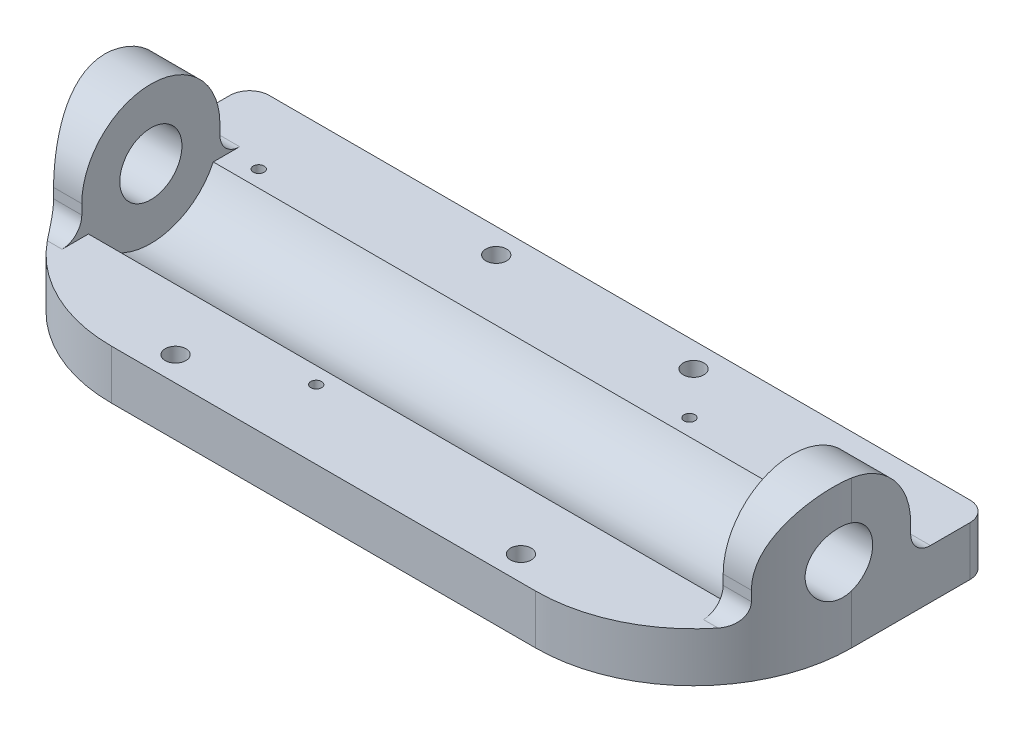
SolidWorks part; units mm, degrees
ref_plane "Front Plane" through (0, 0, 0) normal (0, 0, 1) x (1, 0, 0)
ref_plane "Top Plane" through (0, 0, 0) normal (0, 1, 0) x (1, 0, 0)
ref_plane "Right Plane" through (0, 0, 0) normal (1, 0, 0) x (0, 0, -1)
sketch "Sketch1" plane through (0, 0, 0) normal (1, 0, 0) x (0, 0, -1)
  line L0 (-12.6491, -6) -> (-30, -6)
  line L1 (-30, -6) -> (-30, -16)
  line L2 (-30, -16) -> (30, -16)
  line L3 (30, -16) -> (30, -6)
  line L4 (30, -6) -> (12.6491, -6)
  line L5 (0, 0) -> (0, -16) construction
  arc A0 (-12.6491, -6) -> (12.6491, -6) centre (0, 0) ccw
  dimension "D1" = 14
  dimension "D2" = 16
  dimension "D3" = 60
  dimension "D4" = 10
extrude "Boss-Extrude1" add sketch "Sketch1" along normal blind 75 and the other way blind 75
sketch "Sketch2" plane through (75, 0, 0) normal (1, 0, 0) x (0, 0, -1)
  line L0 (-30, -16) -> (30, -16) construction
  line L1 (-14, 0) -> (-14, -16)
  line L2 (-14, -16) -> (14, -16)
  line L3 (14, -16) -> (14, 0)
  circle A0 centre (0, 0) radius 6.3
  arc A1 (14, 0) -> (-14, 0) centre (0, 0) ccw
  arc A2 (-12.6491, -6) -> (12.6491, -6) centre (0, 0) ccw construction
  dimension "D1" = 12.6
extrude "Boss-Extrude2" add sketch "Sketch2" against normal blind 10
sketch "Sketch3" plane through (-75, 0, 0) normal (-1, 0, 0) x (0, 0, 1)
  line L0 (-14, 0) -> (-14, -16)
  line L1 (30, -16) -> (-30, -16) construction
  line L2 (-14, -16) -> (14, -16)
  line L3 (14, -16) -> (14, 0)
  circle A0 centre (0, 0) radius 6.3
  arc A1 (14, 0) -> (-14, 0) centre (0, 0) ccw
  circle A2 centre (0, 0) radius 6.3 construction
  arc A3 (14, 0) -> (-14, 0) centre (0, 0) ccw construction
extrude "Boss-Extrude3" add sketch "Sketch3" against normal blind 10
sketch "Sketch4" plane through (0, -6, 0) normal (0, 1, 0) x (1, 0, 0)
  circle A0 centre (-15.4853, -16) radius 1.1
  circle A1 centre (-59.1364, 16) radius 1.1
  circle A2 centre (28.1658, 16) radius 1.1
  dimension "D1" = 2.2
extrude "Cut-Extrude1" cut sketch "Sketch4" against normal through all
sketch "Sketch5" plane through (0, -16, 0) normal (0, -1, 0) x (1, 0, 0)
  line L0 (-35, 25) -> (35, 25) construction
  line L1 (-20, -25) -> (20, -25) construction
  line L19 (0, 25) -> (0, -25) construction
  line L20 (-75, 30) -> (75, 30) construction
  circle A0 centre (-35, 25) radius 2.1
  circle A1 centre (35, 25) radius 2.1
  circle A3 centre (-20, -25) radius 2.1
  circle A4 centre (20, -25) radius 2.1
  dimension "D1" = 4.2
  dimension "D2" = 5
  dimension "D3" = 70
  dimension "D4" = 40
extrude "Cut-Extrude2" cut sketch "Sketch5" against normal through all
sketch "Sketch7" plane through (0, -16, 0) normal (0, -1, 0) x (1, 0, 0)
  line L1 (-37.0785, 28.6) -> (-39.1569, 25)
  line L2 (-39.1569, 25) -> (-37.0785, 21.4)
  line L3 (-37.0785, 21.4) -> (-32.9215, 21.4)
  line L4 (-32.9215, 21.4) -> (-30.8431, 25)
  line L5 (-30.8431, 25) -> (-32.9215, 28.6)
  line L6 (-32.9215, 28.6) -> (-37.0785, 28.6)
  line L7 (32.9215, 28.6) -> (30.8431, 25)
  line L8 (30.8431, 25) -> (32.9215, 21.4)
  line L9 (32.9215, 21.4) -> (37.0785, 21.4)
  line L10 (37.0785, 21.4) -> (39.1569, 25)
  line L11 (39.1569, 25) -> (37.0785, 28.6)
  line L12 (37.0785, 28.6) -> (32.9215, 28.6)
  line L19 (-22.0785, -21.4) -> (-24.1569, -25)
  line L20 (-24.1569, -25) -> (-22.0785, -28.6)
  line L21 (-22.0785, -28.6) -> (-17.9215, -28.6)
  line L22 (-17.9215, -28.6) -> (-15.8431, -25)
  line L23 (-15.8431, -25) -> (-17.9215, -21.4)
  line L24 (-17.9215, -21.4) -> (-22.0785, -21.4)
  line L25 (17.9215, -21.4) -> (15.8431, -25)
  line L26 (15.8431, -25) -> (17.9215, -28.6)
  line L27 (17.9215, -28.6) -> (22.0785, -28.6)
  line L28 (22.0785, -28.6) -> (24.1569, -25)
  line L29 (24.1569, -25) -> (22.0785, -21.4)
  line L30 (22.0785, -21.4) -> (17.9215, -21.4)
  circle A0 centre (-35, 25) radius 3.6 construction
  circle A1 centre (35, 25) radius 3.6 construction
  circle A3 centre (-20, -25) radius 3.6 construction
  circle A4 centre (20, -25) radius 3.6 construction
  dimension "D1" = 7.2
extrude "Cut-Extrude3" cut sketch "Sketch7" against normal blind 6
fillet "Fillet1" radius 4 4 edges at (-70, -6, 14) (-70, -6, -14) (70, -6, -14) (70, -6, 14)
fillet "Fillet2" radius 4 2 edges at (-75, -11, -30) (75, -11, -30)
fillet "Fillet3" radius 32 2 edges at (75, -11, 30) (-75, -11, 30)
ref_plane "Plane1" through (-21, 0, 0) normal (-1, 0, 0) x (0, 0, 1)
ref_plane "Plane2" through (22.5, 0, 0) normal (1, 0, 0) x (0, 0, -1)
ref_plane "Plane3" through (-65, 0, 0) normal (-1, 0, 0) x (0, 0, 1)
